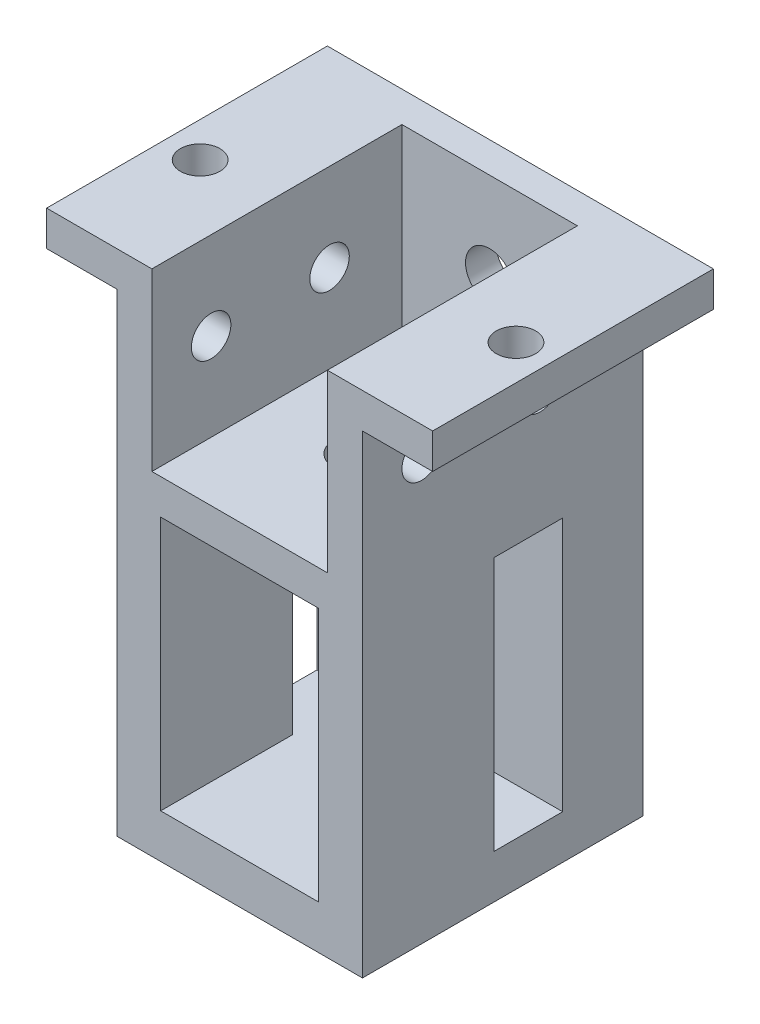
SolidWorks part; units mm, degrees
material "PET"
ref_plane "Front Plane" through (0, 0, 0) normal (0, 0, 1) x (1, 0, 0)
ref_plane "Top Plane" through (0, 0, 0) normal (0, 1, 0) x (1, 0, 0)
ref_plane "Right Plane" through (0, 0, 0) normal (1, 0, 0) x (0, 0, -1)
sketch "Sketch1" plane through (0, 0, 0) normal (0, 0, 1) x (1, 0, 0)
  line L0 (-14, 0) -> (14, 0)
  line L1 (14, 0) -> (14, 20)
  line L2 (14, 20) -> (22, 20)
  line L3 (22, 20) -> (22, 24)
  line L4 (22, 24) -> (10, 24)
  line L5 (10, 24) -> (10, 4)
  line L6 (10, 4) -> (-10, 4)
  line L7 (-10, 4) -> (-10, 24)
  line L8 (-10, 24) -> (-22, 24)
  line L9 (-22, 24) -> (-22, 20)
  line L10 (-22, 20) -> (-14, 20)
  line L11 (-14, 20) -> (-14, 0)
  dimension "D1" = 28
  dimension "D2" = 20
  dimension "D3" = 4
  dimension "D4" = 4
  dimension "D5" = 4
  dimension "D6" = 44
  dimension "D7" = 8
  dimension "D8" = 20
extrude "Boss-Extrude1" add sketch "Sketch1" along normal blind 27
sketch "Sketch2" plane through (-14, 0, 0) normal (-1, 0, 0) x (0, 0, 1)
  line L0 (13.5, 24) -> (13.5, 0) construction
  line L2 (13.5, 24) -> (0, 4) construction
  line L3 (27, 24) -> (0, 24) construction
  line L4 (27, 0) -> (0, 0) construction
  line L5 (13.5, 24) -> (27, 4) construction
  line L6 (27, 0) -> (27, 20) construction
  circle A0 centre (6.75, 14) radius 2.25
  circle A1 centre (20.25, 14) radius 2.25
  dimension "D2" = 4.5
  dimension "D3" = 4.5
  dimension "D1" = 4
extrude "Cut-Extrude1" cut sketch "Sketch2" against normal through all
sketch "Sketch3" plane through (0, 20, 0) normal (0, -1, 0) x (1, 0, 0)
  line L0 (-22, 13.5) -> (22, 13.5) construction
  line L1 (-22, 27) -> (-22, 0) construction
  line L2 (22, 27) -> (22, 0) construction
  circle A0 centre (-18, 13.5) radius 2.25
  circle A1 centre (18, 13.5) radius 2.25
  dimension "D1" = 4.5
  dimension "D2" = 4.5
  dimension "D3" = 36
  dimension "D4" = 4
extrude "Cut-Extrude2" cut sketch "Sketch3" against normal through all
sketch "Sketch5" plane through (0, 0, 0) normal (0, -1, 0) x (1, 0, 0)
  line L0 (14, 27) -> (14, 0) construction
  line L1 (-14, 0) -> (14, 0)
  line L2 (-14, 0) -> (-14, 4.1767)
  line L3 (-14, 4.1767) -> (14, 4.1767)
  line L4 (14, 0) -> (14, 4.1767)
extrude "Boss-Extrude2" add sketch "Sketch5" along normal blind 34
sketch "Sketch6" plane through (0, 0, 4.1767) normal (0, 0, 1) x (1, 0, 0)
  line L0 (14, -34) -> (14, 0) construction
  line L1 (-14, -34) -> (14, -34)
  line L2 (-14, -34) -> (-14, -29)
  line L3 (-14, -29) -> (14, -29)
  line L4 (14, -34) -> (14, -29)
  dimension "D1" = 5
extrude "Boss-Extrude3" add sketch "Sketch6" along normal up to surface (22.8233 mm away) up to face at (0, 15.3333, 27)
sketch "Sketch7" plane through (0, -34, 0) normal (0, -1, 0) x (1, 0, 0)
  line L0 (0, 0) -> (0, 27) construction
  line L1 (-14, 27) -> (14, 27) construction
  circle A0 centre (0, 13.5) radius 2.75
  dimension "D1" = 5.5
extrude "Cut-Extrude3" cut sketch "Sketch7" against normal through all
ref_axis "Axis1" through (0, -29, 13.5) along (0, -1, 0)
ref_plane "Plane1" through (0, 0, 13.5) normal (0, 0, 1) x (1, 0, 0)
sketch "Sketch8" plane through (0, 0, 0) normal (0, -1, 0) x (1, 0, 0)
  line L1 (14, 27) -> (9, 27)
  line L2 (14, 27) -> (14, 12)
  line L3 (14, 12) -> (9, 12)
  line L4 (9, 27) -> (9, 12)
  line L5 (-14, 27) -> (-9, 27)
  line L6 (-14, 27) -> (-14, 12)
  line L7 (-14, 12) -> (-9, 12)
  line L8 (-9, 27) -> (-9, 12)
  dimension "D1" = 5
  dimension "D2" = 5
  dimension "D3" = 15
  dimension "D4" = 15
extrude "Boss-Extrude4" add sketch "Sketch8" along normal up to next
sketch "Sketch9" plane through (0, 0, 0) normal (0, 0, -1) x (-1, 0, 0)
  line L0 (-10, 4) -> (10, 24) construction
  line L1 (-14, -34) -> (14, -34)
  line L2 (-14, -34) -> (-14, 20)
  line L4 (14, -34) -> (14, 20)
  line L5 (14, 20) -> (14, -34) construction
  line L6 (22, 24) -> (-22, 24)
  line L8 (-14, 20) -> (-22, 20)
  line L9 (-22, 24) -> (-22, 20)
  line L12 (14, 20) -> (22, 20)
  line L13 (22, 24) -> (22, 20)
  line L14 (10, 24) -> (22, 24) construction
  circle A0 centre (0, 14) radius 2.75
  dimension "D1" = 5.5
extrude "Boss-Extrude5" add sketch "Sketch9" along normal blind 5
sketch "Sketch10" plane through (0, 0, 0) normal (0, 0, 1) x (1, 0, 0)
  line L1 (-10, 4) -> (10, 4)
  line L2 (-10, 4) -> (-10, 24)
  line L3 (-10, 24) -> (10, 24)
  line L4 (10, 4) -> (10, 24)
extrude "Cut-Extrude4" cut sketch "Sketch10" against normal blind 1.5
